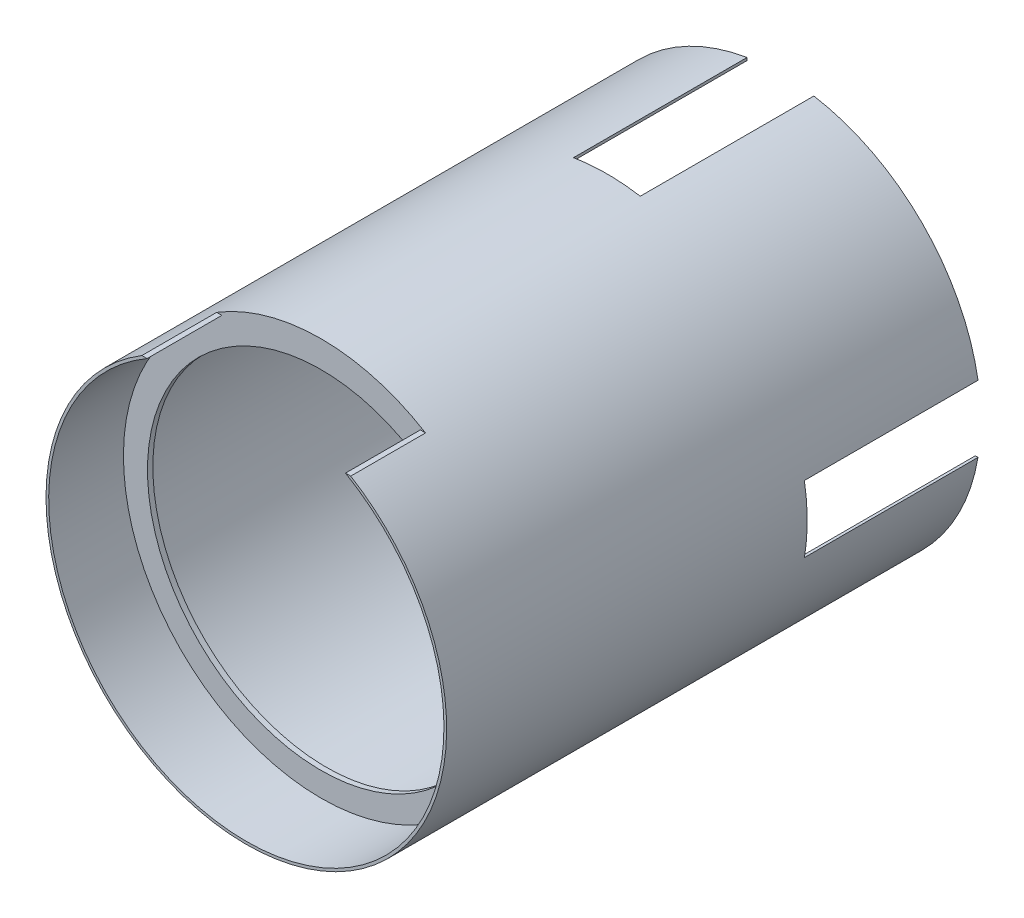
SolidWorks part; units mm, degrees
ref_plane "前视基准面" through (0, 0, 0) normal (0, 0, 1) x (1, 0, 0)
ref_plane "上视基准面" through (0, 0, 0) normal (0, 1, 0) x (1, 0, 0)
ref_plane "右视基准面" through (0, 0, 0) normal (1, 0, 0) x (0, 0, -1)
sketch "草图1" plane through (0, 0, 0) normal (0, 0, 1) x (1, 0, 0)
  circle A0 centre (0, 0) radius 75
  dimension "D1" = 150
extrude "凸台-拉伸1" add sketch "草图1" along normal blind 100 and the other way blind 100
shell "抽壳1" thickness 1 removed face at (75, 0, -100) removed face at (75, 0, 100)
ref_plane "基准面1" through (0, 0, 70) normal (0, 0, 1) x (1, 0, 0)
sketch "草图2" plane through (0, 0, 70) normal (0, 0, 1) x (1, 0, 0)
  circle A0 centre (0, 0) radius 75
  circle A1 centre (0, 0) radius 65
  dimension "D1" = 150
  dimension "D2" = 130
extrude "凸台-拉伸2" add sketch "草图2" along normal blind 2
sketch "草图3" plane through (0, 0, 100) normal (0, 0, 1) x (1, 0, 0)
  line L0 (0, 0) -> (0, 116.4423) construction
  line L1 (39.1024, 64) -> (-39.1024, 64)
  circle A0 centre (0, 0) radius 75 construction
  arc A1 (39.1024, 64) -> (-39.1024, 64) centre (0, 0) ccw
  point P10 (0, 64)
extrude "切除-拉伸1" cut sketch "草图3" against normal up to surface (28 mm away) up to face at (65, 0, 72)
sketch "草图5" plane through (0, 0, 0) normal (0, 1, 0) x (1, 0, 0)
  line L0 (0, 0) -> (0, 70) construction
  line L1 (12.5, 35) -> (-12.5, 35)
  line L2 (12.5, 35) -> (12.5, 105)
  line L3 (12.5, 105) -> (-12.5, 105)
  line L4 (-12.5, 35) -> (-12.5, 105)
  line L5 (12.5, 35) -> (-12.5, 105) construction
  line L6 (12.5, 105) -> (-12.5, 35) construction
  point P0 (0, 70)
  dimension "D1" = 70
  dimension "D2" = 35
  dimension "D3" = 25
extrude "切除-拉伸2" cut sketch "草图5" against normal through all and the other way through all
pattern_circular "阵列(圆周)1" count 4 over 360 about axis through (0, 0, -100) along (0, 0, 1) of "切除-拉伸2"
